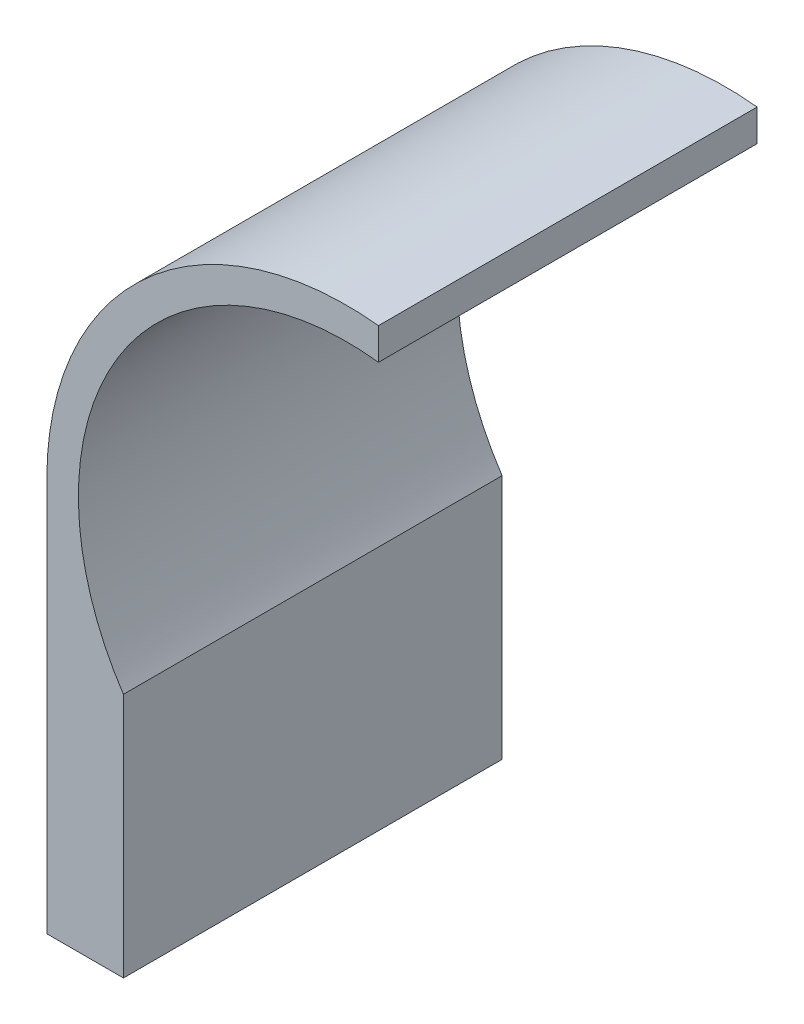
SolidWorks part; units mm, degrees
material "201 Annealed Stainless Steel (SS)"
ref_plane "Front Plane" through (0, 0, 0) normal (0, 0, 1) x (1, 0, 0)
ref_plane "Top Plane" through (0, 0, 0) normal (0, 1, 0) x (1, 0, 0)
ref_plane "Right Plane" through (0, 0, 0) normal (1, 0, 0) x (0, 0, -1)
sketch "Sketch1" plane through (0, 0, 0) normal (0, 0, 1) x (1, 0, 0)
  line L0 (0, 0) -> (0, -95) construction
  line L1 (-70.7312, -47.1391) -> (70.7312, -47.1391) construction
  line L2 (0, 0) -> (101.5936, 0) construction
  line L3 (10.1, 111.7322) -> (10.1, -25.0367) construction
  line L4 (-70.7312, -47.1391) -> (-70.7312, -63.42)
  line L5 (10.1, 94.4616) -> (10.1, 84.3978)
  line L6 (-70.7312, -63.42) -> (-70.7312, -125)
  line L7 (0, 0) -> (-138.7196, 0) construction
  line L8 (-95, 0) -> (-95, -125)
  line L9 (-70.7312, -125) -> (-95, -125)
  line L10 (0, -95) -> (0, -125) construction
  line L11 (0, -125) -> (-118.3636, -125) construction
  circle A0 centre (0, 0) radius 85 construction
  circle A1 centre (0, 0) radius 95 construction
  arc A2 (-70.7312, -47.1391) -> (10.1, 84.3978) centre (0, 0) cw
  arc A3 (-95, 0) -> (10.1, 94.4616) centre (0, 0) cw
  dimension "D1" = 170
  dimension "D2" = 190
  dimension "D6" = 95
  dimension "D5" = 30
  dimension "D3" = 167.1
  dimension "D4" = 10.1
extrude "Inner Ring - Left Side" add sketch "Sketch1" along normal blind 120
